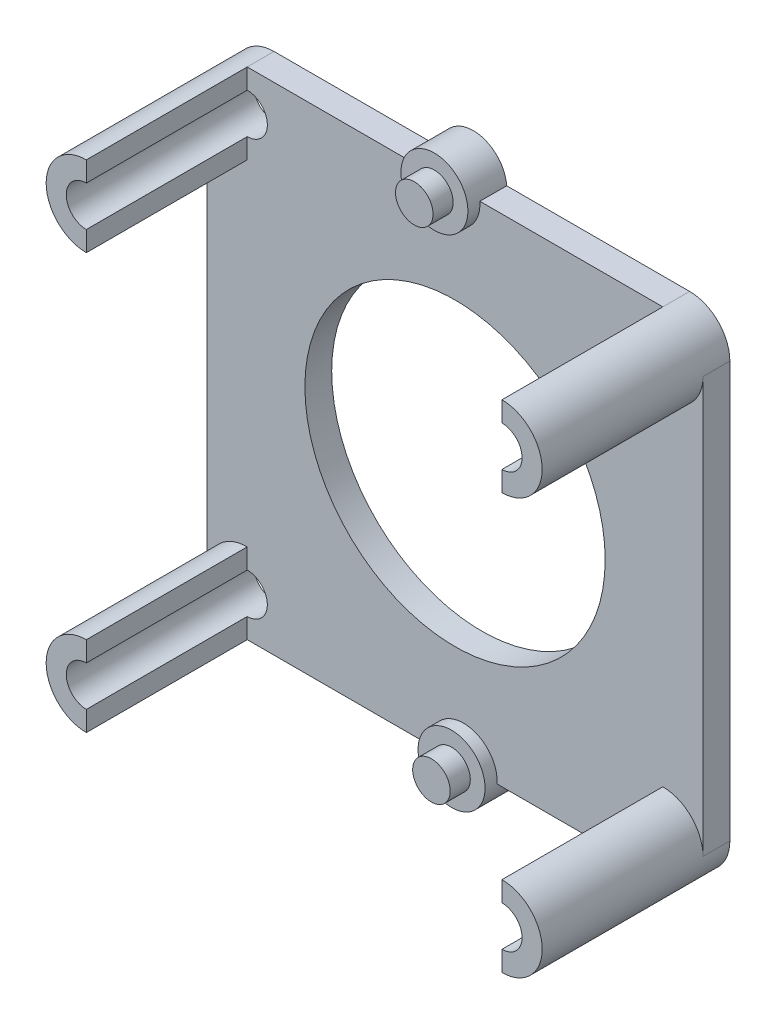
SolidWorks part; units mm, degrees
ref_plane "Front Plane" through (0, 0, 0) normal (0, 0, 1) x (1, 0, 0)
ref_plane "Top Plane" through (0, 0, 0) normal (0, 1, 0) x (1, 0, 0)
ref_plane "Right Plane" through (0, 0, 0) normal (1, 0, 0) x (0, 0, -1)
sketch "Sketch1" plane through (0, 0, 0) normal (0, 0, 1) x (1, 0, 0)
  line L0 (0, 0) -> (17.311, 13.1083) construction
  line L1 (0, 0) -> (-17.311, 13.1083) construction
  line L2 (15.5, 18.5) -> (-15.5, 18.5) construction
  line L3 (-18.5, 15.5) -> (-18.5, -15.5)
  line L4 (18.5, 15.5) -> (18.5, -15.5)
  line L5 (0, 0) -> (-0.6397, 18.32) construction
  line L6 (0, 0) -> (99.0761, 0) construction
  line L7 (15.5, -18.5) -> (-15.5, -18.5) construction
  line L8 (15.5, 18.5) -> (1.8538, 18.5)
  line L9 (-3.1333, 18.5) -> (-15.5, 18.5)
  line L10 (0, 0) -> (1.1952, -34.2261) construction
  line L11 (15.5, -18.5) -> (3.1333, -18.5)
  line L12 (-1.8538, -18.5) -> (-15.5, -18.5)
  circle A0 centre (0, 0) radius 11.2 construction
  circle A1 centre (15.5, 15.5) radius 1.5
  circle A2 centre (-15.5, 15.5) radius 1.5
  circle A3 centre (15.5, 15.5) radius 3 construction
  circle A4 centre (-15.5, 15.5) radius 3 construction
  circle A5 centre (0, 0) radius 11.2
  arc A6 (15.5, 18.5) -> (18.5, 15.5) centre (15.5, 15.5) cw
  arc A7 (18.5, -15.5) -> (15.5, -18.5) centre (15.5, -15.5) cw
  circle A8 centre (-0.6397, 18.32) radius 2.5 construction
  arc A9 (-3.1333, 18.5) -> (1.8538, 18.5) centre (-0.6397, 18.32) cw
  circle A10 centre (15.5, -15.5) radius 1.5
  circle A11 centre (-15.5, -15.5) radius 1.5
  circle A12 centre (15.5, -15.5) radius 3 construction
  circle A13 centre (-15.5, -15.5) radius 3 construction
  arc A14 (-15.5, -18.5) -> (-18.5, -15.5) centre (-15.5, -15.5) cw
  arc A15 (-18.5, 15.5) -> (-15.5, 18.5) centre (-15.5, 15.5) cw
  circle A16 centre (0.6397, -18.32) radius 2.5 construction
  arc A17 (-1.8538, -18.5) -> (3.1333, -18.5) centre (0.6397, -18.32) ccw
  point P0 (0, 0)
  point P1 (15.5, 15.5)
  point P3 (-15.5, 15.5)
  point P20 (-0.6397, 18.32)
  point P25 (-15.5, -15.5)
  point P26 (15.5, -15.5)
  point P37 (0.6397, -18.32)
  dimension "D1" = 15.5
  dimension "D5" = 18.3312
  dimension "D6" = 15.5
  dimension "D10" = 92
  dimension "D2" = 15.5
  dimension "D3" = 15.5
  dimension "D4" = 15.5
  dimension "D7" = 15.5
  dimension "D8" = 15.5
  dimension "D9" = 15.5
  dimension "AXIS_DIST" = 18.3312
extrude "Extrude1" add sketch "Sketch1" along normal blind 2
sketch "Sketch2" plane through (0, 0, 2) normal (0, 0, 1) x (1, 0, 0)
  circle A0 centre (-0.6397, 18.32) radius 2.5
  circle A1 centre (0.6397, -18.32) radius 2.5
extrude "Extrude2" add sketch "Sketch2" along normal blind 0.9
sketch "Sketch3" plane through (0, 0, 2.9) normal (0, 0, 1) x (1, 0, 0)
  circle A0 centre (-0.6397, 18.32) radius 1.4
  circle A1 centre (0.6397, -18.32) radius 1.4
extrude "Extrude3" add sketch "Sketch3" along normal blind 1.5
sketch "Sketch4" plane through (0, 0, 2) normal (0, 0, 1) x (1, 0, 0)
  line L0 (3.1333, -18.5) -> (15.5, -18.5) construction
  line L1 (15.5, -14) -> (15.5, -12.5)
  line L2 (15.5, -17) -> (15.5, -18.5)
  line L3 (-15.5, -14) -> (-15.5, -12.5)
  line L4 (-15.5, -17) -> (-15.5, -18.5)
  line L5 (-15.5, 17) -> (-15.5, 18.5)
  line L6 (-15.5, 14) -> (-15.5, 12.5)
  line L7 (15.5, 17) -> (15.5, 18.5)
  line L8 (15.5, 14) -> (15.5, 12.5)
  circle A0 centre (-15.5, 15.5) radius 1.5 construction
  circle A1 centre (15.5, 15.5) radius 1.5 construction
  circle A2 centre (15.5, -15.5) radius 1.5 construction
  circle A3 centre (-15.5, -15.5) radius 1.5 construction
  arc A4 (-15.5, 17) -> (-15.5, 14) centre (-15.5, 15.5) ccw
  arc A5 (-15.5, 18.5) -> (-15.5, 12.5) centre (-15.5, 15.5) ccw
  arc A6 (15.5, 14) -> (15.5, 17) centre (15.5, 15.5) ccw
  arc A7 (15.5, 18.5) -> (15.5, 12.5) centre (15.5, 15.5) cw
  arc A8 (-15.5, -14) -> (-15.5, -17) centre (-15.5, -15.5) ccw
  arc A9 (-15.5, -18.5) -> (-15.5, -12.5) centre (-15.5, -15.5) cw
  arc A10 (15.5, -14) -> (15.5, -17) centre (15.5, -15.5) cw
  arc A11 (15.5, -18.5) -> (15.5, -12.5) centre (15.5, -15.5) ccw
  arc A12 (15.5, -18.5) -> (18.5, -15.5) centre (15.5, -15.5) ccw construction
  point P0 (-15.5, 14)
  point P1 (-15.5, 17)
  point P4 (15.5, 14)
  point P5 (15.5, 17)
  point P8 (15.5, -17)
  point P9 (15.5, -14)
  point P12 (-15.5, -17)
  point P13 (-15.5, -14)
  point P16 (-15.5, 18.5)
  point P17 (15.5, 18.5)
extrude "Extrude4" add sketch "Sketch4" along normal blind 12
equation "\"D5@Sketch1\" = \"AXIS_DIST\""
